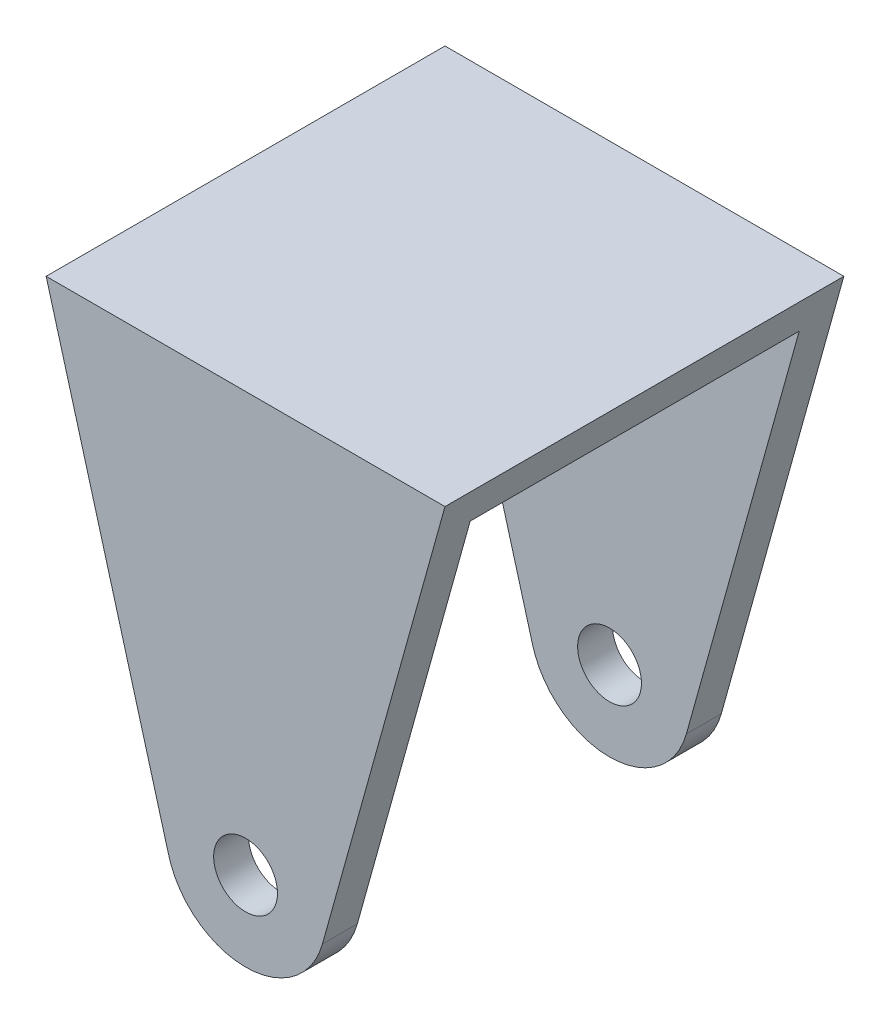
SolidWorks part; units mm, degrees
ref_plane "Front Plane" through (0, 0, 0) normal (0, 0, 1) x (1, 0, 0)
ref_plane "Top Plane" through (0, 0, 0) normal (0, 1, 0) x (1, 0, 0)
ref_plane "Right Plane" through (0, 0, 0) normal (1, 0, 0) x (0, 0, -1)
sketch "Sketch1" plane through (0, 0, 0) normal (0, 0, 1) x (1, 0, 0)
  circle A0 centre (0, 0) radius 3
  circle A1 centre (0, 0) radius 5.5
  dimension "D1" = 6
  dimension "D2" = 11
extrude "Boss-Extrude1" add sketch "Sketch1" along normal blind 30
sketch "Sketch2" plane through (0, 0, 0) normal (0, 0, 1) x (1, 0, 0)
  line L0 (20, 42) -> (-20, 42)
  line L1 (20, 42) -> (7.7068, -2.1461)
  line L2 (-20, 42) -> (-7.7412, -2.0183)
  circle A0 centre (0, 0) radius 8
  point P9 (0, 42)
  dimension "D1" = 16
  dimension "D2" = 42
  dimension "D3" = 40
extrude "Boss-Extrude2" add sketch "Sketch2" along normal blind 40 from offset 5 contours A0 L1 L0 L2 | A0 region at (0.0003, 25.7756, 0) region at (0, 0, 0) offset against normal yes
sketch "Sketch3" plane through (0, 0, 0) normal (1, 0, 0) x (0, 0, -1)
  line L0 (-35, -8) -> (5, -8) construction
  line L1 (-31.5, -8) -> (1.5, -8)
  line L2 (-31.5, -8) -> (-31.5, 38.5)
  line L3 (-31.5, 38.5) -> (1.5, 38.5)
  line L4 (1.5, -8) -> (1.5, 38.5)
  line L6 (-35, 42) -> (5, 42) construction
  point P6 (-15, 42)
  point P9 (-15, 38.5)
  dimension "D1" = 33
  dimension "D2" = 3.5
extrude "Cut-Extrude1" cut sketch "Sketch3" against normal through all both and the other way through all
sketch "Sketch4" plane through (0, 0, 35) normal (0, 0, 1) x (1, 0, 0)
  circle A0 centre (0, 0) radius 3.2
  dimension "D1" = 6.4
extrude "Cut-Extrude2" cut sketch "Sketch4" against normal through all both and the other way through all
